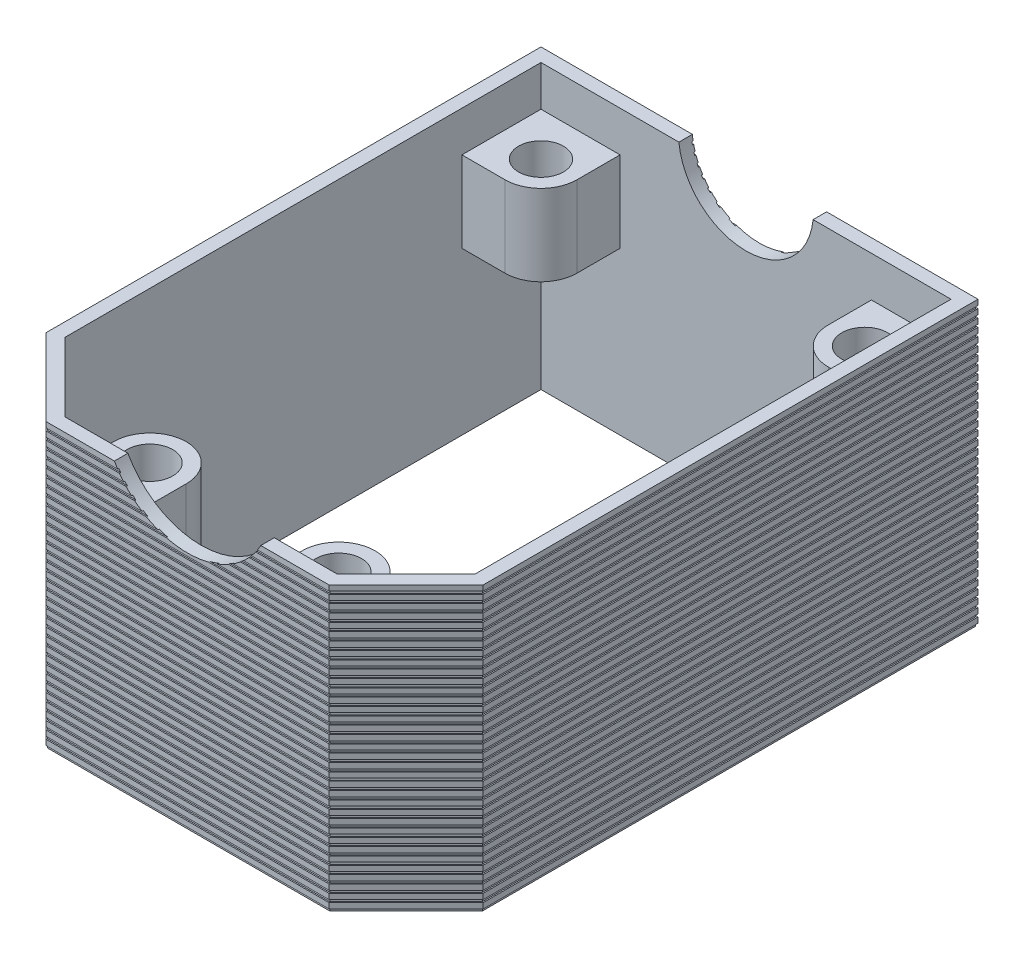
SolidWorks part; units mm, degrees
ref_plane "Front" through (0, 0, 0) normal (0, 0, 1) x (1, 0, 0)
ref_plane "Top" through (0, 0, 0) normal (0, 1, 0) x (1, 0, 0)
ref_plane "Right" through (0, 0, 0) normal (1, 0, 0) x (0, 0, -1)
sketch "Sketch1" plane through (0, 0, 0) normal (0, 1, 0) x (1, 0, 0)
  line L1 (10, -20) -> (-10, -20)
  line L2 (15, -15) -> (15, 20)
  line L3 (15, 20) -> (-15, 20)
  line L4 (-15, -15) -> (-15, 20)
  line L5 (15, -20) -> (-15, 20) construction
  line L6 (15, 20) -> (-15, -20) construction
  line L7 (-15, -15) -> (-10, -20)
  line L10 (10, -20) -> (15, -15)
  circle A0 centre (-12, 17) radius 1.4615
  circle A1 centre (12, 17) radius 1.5
  circle A2 centre (7, -17) radius 1.5
  circle A3 centre (-7, -17) radius 1.5
  point P0 (0, 0)
  dimension "D7" = 3
  dimension "D1" = 30
  dimension "D2" = 40
  dimension "D3" = 5
  dimension "D4" = 5
  dimension "D5" = 5
  dimension "D6" = 5
  dimension "D8" = 3
  dimension "D9" = 3
  dimension "D10" = 3
  dimension "D11" = 3
  dimension "D12" = 3
  dimension "D13" = 3
  dimension "D14" = 3
sketch "Sketch2" plane through (0, 0, 0) normal (0, 1, 0) x (1, 0, 0)
  line L0 (-15.2, 20.2) -> (15.2, 20.2)
  line L1 (15.2, 20.2) -> (15.2, -15.0828)
  line L2 (15.2, -15.0828) -> (10.0828, -20.2)
  line L3 (10.0828, -20.2) -> (-10.0828, -20.2)
  line L4 (-10.0828, -20.2) -> (-15.2, -15.0828)
  line L5 (-15.2, -15.0828) -> (-15.2, 20.2)
  line L6 (-16.2, 21.2) -> (16.2, 21.2)
  line L7 (16.2, 21.2) -> (16.2, -15.4971)
  line L8 (16.2, -15.4971) -> (10.4971, -21.2)
  line L9 (10.4971, -21.2) -> (-10.4971, -21.2)
  line L10 (-10.4971, -21.2) -> (-16.2, -15.4971)
  line L11 (-16.2, -15.4971) -> (-16.2, 21.2)
  line L12 (15, 20) -> (-15, 20) construction
  line L13 (15, -15) -> (15, 20) construction
  line L14 (-15, -15) -> (-15, 20) construction
  line L16 (10, -20) -> (-10, -20) construction
  line L17 (-15, -15) -> (-10, -20) construction
  line L19 (10, -20) -> (15, -15) construction
  dimension "D1" = 0.2
  dimension "D2" = 0.2
  dimension "D3" = 0.2
  dimension "D4" = 0.2
  dimension "D5" = 0.2
  dimension "D6" = 0.2
  dimension "D7" = 1
  dimension "D8" = 1
  dimension "D9" = 1
  dimension "D10" = 1
  dimension "D11" = 1
  dimension "D12" = 1
extrude "Boss-Extrude1" add sketch "Sketch2" along normal blind 9 and the other way blind 12
sketch "Sketch4" plane through (0, 0, 0) normal (0, 1, 0) x (1, 0, 0)
  line L1 (15.2, 20.2) -> (-15.2, 20.2) construction
  line L6 (9.3, 17) -> (9.3, 20.2)
  line L7 (12, 14.3) -> (15.2, 14.3)
  line L8 (15.2, -15.0828) -> (15.2, 20.2) construction
  line L9 (15.2, 14.3) -> (15.2, 20.2)
  line L10 (15.2, 20.2) -> (9.3, 20.2)
  line L11 (-9.7, -17) -> (-9.7, -20.2)
  line L12 (-10.0828, -20.2) -> (10.0828, -20.2) construction
  line L13 (-9.7, -20.2) -> (-4.3, -20.2)
  line L14 (-4.3, -20.2) -> (-4.3, -17)
  line L15 (4.3, -17) -> (4.3, -20.2)
  line L16 (4.3, -20.2) -> (9.7, -20.2)
  line L17 (9.7, -20.2) -> (9.7, -17)
  line L21 (-9.3385, 17) -> (-9.3385, 20.2)
  line L22 (-9.3385, 20.2) -> (-15.2, 20.2)
  line L23 (-15.2, 20.2) -> (-15.2, 14.3385)
  line L24 (-15.2, 20.2) -> (-15.2, -15.0828) construction
  line L25 (-15.2, 14.3385) -> (-12, 14.3385)
  circle A0 centre (-12, 17) radius 1.6615
  circle A1 centre (12, 17) radius 1.7
  arc A2 (9.3, 17) -> (12, 14.3) centre (12, 17) ccw
  circle A4 centre (-7, -17) radius 1.7
  arc A5 (-4.3, -17) -> (-9.7, -17) centre (-7, -17) ccw
  circle A6 centre (7, -17) radius 1.7
  arc A7 (9.7, -17) -> (4.3, -17) centre (7, -17) ccw
  circle A8 centre (-7, -17) radius 1.5 construction
  circle A9 centre (7, -17) radius 1.5 construction
  circle A10 centre (12, 17) radius 1.5 construction
  circle A11 centre (-12, 17) radius 1.4615 construction
  arc A13 (-12, 14.3385) -> (-9.3385, 17) centre (-12, 17) ccw
  dimension "D1" = 0.2
  dimension "D2" = 1
  dimension "D3" = 0.2
  dimension "D4" = 1
  dimension "D5" = 0.2
  dimension "D6" = 1
  dimension "D7" = 0.2
  dimension "D8" = 1
extrude "Boss-Extrude2" add sketch "Sketch4" along normal blind 6
sketch "Sketch5" plane through (0, 0, -21.2) normal (0, 0, -1) x (-1, 0, 0)
  line L6 (-17.0656, 9.5) -> (18.9737, 9.5) construction
  line L7 (-10, 0) -> (10, 0) construction
  circle A1 centre (0, 9.5) radius 5
  dimension "D2" = 10
  dimension "D1" = 9.5
sketch "Sketch6" plane through (0, 0, 21.2) normal (0, 0, 1) x (1, 0, 0)
  line L0 (-10.4971, 9) -> (10.4971, 9) construction
  circle A0 centre (0, 12) radius 6.2
  dimension "D1" = 12.4
  dimension "D2" = 3
extrude "Cut-Extrude4" cut sketch "Sketch6" against normal up to surface (1 mm away) up to face at (-7, 3, 20.2)
extrude "Cut-Extrude5" cut sketch "Sketch5" against normal up to surface (1 mm away) up to face at (-0.0064, 1.5, -20.2)
sketch "Sketch7" plane through (0, 0, -21.2) normal (0, 0, -1) x (-1, 0, 0)
  line L0 (16.2, -12) -> (16.2, 9) construction
  line L1 (-16.2, -12) -> (16.2, -12)
  line L2 (-16.2, -12) -> (-16.2, -11.8)
  line L3 (-16.2, -11.8) -> (16.2, -11.8)
  line L4 (16.2, -12) -> (16.2, -11.8)
  line L289 (-16.2, -11.4) -> (16.2, -11.4)
  line L290 (-16.2, -11.4) -> (-16.2, -11.2)
  line L291 (-16.2, -11.2) -> (16.2, -11.2)
  line L292 (16.2, -11.4) -> (16.2, -11.2)
  line L293 (-16.2, -10.8) -> (16.2, -10.8)
  line L294 (-16.2, -10.8) -> (-16.2, -10.6)
  line L295 (-16.2, -10.6) -> (16.2, -10.6)
  line L296 (16.2, -10.8) -> (16.2, -10.6)
  line L297 (-16.2, -10.2) -> (16.2, -10.2)
  line L298 (-16.2, -10.2) -> (-16.2, -10)
  line L299 (-16.2, -10) -> (16.2, -10)
  line L300 (16.2, -10.2) -> (16.2, -10)
  line L301 (-16.2, -9.6) -> (16.2, -9.6)
  line L302 (-16.2, -9.6) -> (-16.2, -9.4)
  line L303 (-16.2, -9.4) -> (16.2, -9.4)
  line L304 (16.2, -9.6) -> (16.2, -9.4)
  line L305 (-16.2, -9) -> (16.2, -9)
  line L306 (-16.2, -9) -> (-16.2, -8.8)
  line L307 (-16.2, -8.8) -> (16.2, -8.8)
  line L308 (16.2, -9) -> (16.2, -8.8)
  line L309 (-16.2, -8.4) -> (16.2, -8.4)
  line L310 (-16.2, -8.4) -> (-16.2, -8.2)
  line L311 (-16.2, -8.2) -> (16.2, -8.2)
  line L312 (16.2, -8.4) -> (16.2, -8.2)
  line L313 (-16.2, -7.8) -> (16.2, -7.8)
  line L314 (-16.2, -7.8) -> (-16.2, -7.6)
  line L315 (-16.2, -7.6) -> (16.2, -7.6)
  line L316 (16.2, -7.8) -> (16.2, -7.6)
  line L317 (-16.2, -7.2) -> (16.2, -7.2)
  line L318 (-16.2, -7.2) -> (-16.2, -7)
  line L319 (-16.2, -7) -> (16.2, -7)
  line L320 (16.2, -7.2) -> (16.2, -7)
  line L321 (-16.2, -6.6) -> (16.2, -6.6)
  line L322 (-16.2, -6.6) -> (-16.2, -6.4)
  line L323 (-16.2, -6.4) -> (16.2, -6.4)
  line L324 (16.2, -6.6) -> (16.2, -6.4)
  line L325 (-16.2, -6) -> (16.2, -6)
  line L326 (-16.2, -6) -> (-16.2, -5.8)
  line L327 (-16.2, -5.8) -> (16.2, -5.8)
  line L328 (16.2, -6) -> (16.2, -5.8)
  line L329 (-16.2, -5.4) -> (16.2, -5.4)
  line L330 (-16.2, -5.4) -> (-16.2, -5.2)
  line L331 (-16.2, -5.2) -> (16.2, -5.2)
  line L332 (16.2, -5.4) -> (16.2, -5.2)
  line L333 (-16.2, -4.8) -> (16.2, -4.8)
  line L334 (-16.2, -4.8) -> (-16.2, -4.6)
  line L335 (-16.2, -4.6) -> (16.2, -4.6)
  line L336 (16.2, -4.8) -> (16.2, -4.6)
  line L337 (-16.2, -4.2) -> (16.2, -4.2)
  line L338 (-16.2, -4.2) -> (-16.2, -4)
  line L339 (-16.2, -4) -> (16.2, -4)
  line L340 (16.2, -4.2) -> (16.2, -4)
  line L341 (-16.2, -3.6) -> (16.2, -3.6)
  line L342 (-16.2, -3.6) -> (-16.2, -3.4)
  line L343 (-16.2, -3.4) -> (16.2, -3.4)
  line L344 (16.2, -3.6) -> (16.2, -3.4)
  line L345 (-16.2, -3) -> (16.2, -3)
  line L346 (-16.2, -3) -> (-16.2, -2.8)
  line L347 (-16.2, -2.8) -> (16.2, -2.8)
  line L348 (16.2, -3) -> (16.2, -2.8)
  line L349 (-16.2, -2.4) -> (16.2, -2.4)
  line L350 (-16.2, -2.4) -> (-16.2, -2.2)
  line L351 (-16.2, -2.2) -> (16.2, -2.2)
  line L352 (16.2, -2.4) -> (16.2, -2.2)
  line L353 (-16.2, -1.8) -> (16.2, -1.8)
  line L354 (-16.2, -1.8) -> (-16.2, -1.6)
  line L355 (-16.2, -1.6) -> (16.2, -1.6)
  line L356 (16.2, -1.8) -> (16.2, -1.6)
  line L357 (-16.2, -1.2) -> (16.2, -1.2)
  line L358 (-16.2, -1.2) -> (-16.2, -1)
  line L359 (-16.2, -1) -> (16.2, -1)
  line L360 (16.2, -1.2) -> (16.2, -1)
  line L361 (-16.2, -0.6) -> (16.2, -0.6)
  line L362 (-16.2, -0.6) -> (-16.2, -0.4)
  line L363 (-16.2, -0.4) -> (16.2, -0.4)
  line L364 (16.2, -0.6) -> (16.2, -0.4)
  line L365 (-16.2, 0) -> (16.2, 0)
  line L366 (-16.2, 0) -> (-16.2, 0.2)
  line L367 (-16.2, 0.2) -> (16.2, 0.2)
  line L368 (16.2, 0) -> (16.2, 0.2)
  line L369 (-16.2, 0.6) -> (16.2, 0.6)
  line L370 (-16.2, 0.6) -> (-16.2, 0.8)
  line L371 (-16.2, 0.8) -> (16.2, 0.8)
  line L372 (16.2, 0.6) -> (16.2, 0.8)
  line L373 (-16.2, 1.2) -> (16.2, 1.2)
  line L374 (-16.2, 1.2) -> (-16.2, 1.4)
  line L375 (-16.2, 1.4) -> (16.2, 1.4)
  line L376 (16.2, 1.2) -> (16.2, 1.4)
  line L377 (-16.2, 1.8) -> (16.2, 1.8)
  line L378 (-16.2, 1.8) -> (-16.2, 2)
  line L379 (-16.2, 2) -> (16.2, 2)
  line L380 (16.2, 1.8) -> (16.2, 2)
  line L381 (-16.2, 2.4) -> (16.2, 2.4)
  line L382 (-16.2, 2.4) -> (-16.2, 2.6)
  line L383 (-16.2, 2.6) -> (16.2, 2.6)
  line L384 (16.2, 2.4) -> (16.2, 2.6)
  line L385 (-16.2, 3) -> (16.2, 3)
  line L386 (-16.2, 3) -> (-16.2, 3.2)
  line L387 (-16.2, 3.2) -> (16.2, 3.2)
  line L388 (16.2, 3) -> (16.2, 3.2)
  line L389 (-16.2, 3.6) -> (16.2, 3.6)
  line L390 (-16.2, 3.6) -> (-16.2, 3.8)
  line L391 (-16.2, 3.8) -> (16.2, 3.8)
  line L392 (16.2, 3.6) -> (16.2, 3.8)
  line L393 (-16.2, 4.2) -> (16.2, 4.2)
  line L394 (-16.2, 4.2) -> (-16.2, 4.4)
  line L395 (-16.2, 4.4) -> (16.2, 4.4)
  line L396 (16.2, 4.2) -> (16.2, 4.4)
  line L397 (-16.2, 4.8) -> (16.2, 4.8)
  line L398 (-16.2, 4.8) -> (-16.2, 5)
  line L399 (-16.2, 5) -> (16.2, 5)
  line L400 (16.2, 4.8) -> (16.2, 5)
  line L401 (-16.2, 5.4) -> (16.2, 5.4)
  line L402 (-16.2, 5.4) -> (-16.2, 5.6)
  line L403 (-16.2, 5.6) -> (16.2, 5.6)
  line L404 (16.2, 5.4) -> (16.2, 5.6)
  line L405 (-16.2, 6) -> (16.2, 6)
  line L406 (-16.2, 6) -> (-16.2, 6.2)
  line L407 (-16.2, 6.2) -> (16.2, 6.2)
  line L408 (16.2, 6) -> (16.2, 6.2)
  line L409 (-16.2, 6.6) -> (16.2, 6.6)
  line L410 (-16.2, 6.6) -> (-16.2, 6.8)
  line L411 (-16.2, 6.8) -> (16.2, 6.8)
  line L412 (16.2, 6.6) -> (16.2, 6.8)
  line L413 (-16.2, 7.2) -> (16.2, 7.2)
  line L414 (-16.2, 7.2) -> (-16.2, 7.4)
  line L415 (-16.2, 7.4) -> (16.2, 7.4)
  line L416 (16.2, 7.2) -> (16.2, 7.4)
  line L417 (-16.2, 7.8) -> (16.2, 7.8)
  line L418 (-16.2, 7.8) -> (-16.2, 8)
  line L419 (-16.2, 8) -> (16.2, 8)
  line L420 (16.2, 7.8) -> (16.2, 8)
  line L421 (-16.2, 8.4) -> (16.2, 8.4)
  line L422 (-16.2, 8.4) -> (-16.2, 8.6)
  line L423 (-16.2, 8.6) -> (16.2, 8.6)
  line L424 (16.2, 8.4) -> (16.2, 8.6)
  line L425 (-16.2, 9) -> (16.2, 9)
  line L426 (-16.2, 9) -> (-16.2, 9.2)
  line L427 (-16.2, 9.2) -> (16.2, 9.2)
  line L428 (16.2, 9) -> (16.2, 9.2)
  line L429 (-16.2, 9.6) -> (16.2, 9.6)
  line L430 (-16.2, 9.6) -> (-16.2, 9.8)
  line L431 (-16.2, 9.8) -> (16.2, 9.8)
  line L432 (16.2, 9.6) -> (16.2, 9.8)
  line L433 (-16.2, 10.2) -> (16.2, 10.2)
  line L434 (-16.2, 10.2) -> (-16.2, 10.4)
  line L435 (-16.2, 10.4) -> (16.2, 10.4)
  line L436 (16.2, 10.2) -> (16.2, 10.4)
  line L437 (-16.2, 10.8) -> (16.2, 10.8)
  line L438 (-16.2, 10.8) -> (-16.2, 11)
  line L439 (-16.2, 11) -> (16.2, 11)
  line L440 (16.2, 10.8) -> (16.2, 11)
  line L441 (-16.2, 11.4) -> (16.2, 11.4)
  line L442 (-16.2, 11.4) -> (-16.2, 11.6)
  line L443 (-16.2, 11.6) -> (16.2, 11.6)
  line L444 (16.2, 11.4) -> (16.2, 11.6)
  dimension "D1" = 0.2
  dimension "D2" = 40
extrude "Cut-Extrude6" cut sketch "Sketch7" against normal blind 0.09
sketch "Sketch8" plane through (16.2, 0, 0) normal (1, 0, 0) x (0, 0, -1)
  line L129 (-15.4971, -11.4) -> (-15.4971, -11.2)
  line L130 (-15.4971, -12) -> (21.11, -12)
  line L131 (-15.4971, -12) -> (-15.4971, -11.8)
  line L132 (-15.4971, -11.8) -> (21.11, -11.8)
  line L133 (21.11, -12) -> (21.11, -11.8)
  line L134 (-15.4971, -11.4) -> (21.11, -11.4)
  line L135 (21.11, -11.4) -> (21.11, -11.2)
  line L136 (-15.4971, -11.2) -> (21.11, -11.2)
  line L137 (-15.4971, -10.8) -> (-15.4971, -10.6)
  line L138 (-15.4971, -10.8) -> (21.11, -10.8)
  line L139 (21.11, -10.8) -> (21.11, -10.6)
  line L140 (-15.4971, -10.6) -> (21.11, -10.6)
  line L141 (-15.4971, -10.2) -> (-15.4971, -10)
  line L142 (-15.4971, -10.2) -> (21.11, -10.2)
  line L143 (21.11, -10.2) -> (21.11, -10)
  line L144 (-15.4971, -10) -> (21.11, -10)
  line L145 (-15.4971, -9.6) -> (-15.4971, -9.4)
  line L146 (-15.4971, -9.6) -> (21.11, -9.6)
  line L147 (21.11, -9.6) -> (21.11, -9.4)
  line L148 (-15.4971, -9.4) -> (21.11, -9.4)
  line L149 (-15.4971, -9) -> (-15.4971, -8.8)
  line L150 (-15.4971, -9) -> (21.11, -9)
  line L151 (21.11, -9) -> (21.11, -8.8)
  line L152 (-15.4971, -8.8) -> (21.11, -8.8)
  line L153 (-15.4971, -8.4) -> (-15.4971, -8.2)
  line L154 (-15.4971, -8.4) -> (21.11, -8.4)
  line L155 (21.11, -8.4) -> (21.11, -8.2)
  line L156 (-15.4971, -8.2) -> (21.11, -8.2)
  line L157 (-15.4971, -7.8) -> (-15.4971, -7.6)
  line L158 (-15.4971, -7.8) -> (21.11, -7.8)
  line L159 (21.11, -7.8) -> (21.11, -7.6)
  line L160 (-15.4971, -7.6) -> (21.11, -7.6)
  line L161 (-15.4971, -7.2) -> (-15.4971, -7)
  line L162 (-15.4971, -7.2) -> (21.11, -7.2)
  line L163 (21.11, -7.2) -> (21.11, -7)
  line L164 (-15.4971, -7) -> (21.11, -7)
  line L165 (-15.4971, -6.6) -> (-15.4971, -6.4)
  line L166 (-15.4971, -6.6) -> (21.11, -6.6)
  line L167 (21.11, -6.6) -> (21.11, -6.4)
  line L168 (-15.4971, -6.4) -> (21.11, -6.4)
  line L169 (-15.4971, -6) -> (-15.4971, -5.8)
  line L170 (-15.4971, -6) -> (21.11, -6)
  line L171 (21.11, -6) -> (21.11, -5.8)
  line L172 (-15.4971, -5.8) -> (21.11, -5.8)
  line L173 (-15.4971, -5.4) -> (-15.4971, -5.2)
  line L174 (-15.4971, -5.4) -> (21.11, -5.4)
  line L175 (21.11, -5.4) -> (21.11, -5.2)
  line L176 (-15.4971, -5.2) -> (21.11, -5.2)
  line L177 (-15.4971, -4.8) -> (-15.4971, -4.6)
  line L178 (-15.4971, -4.8) -> (21.11, -4.8)
  line L179 (21.11, -4.8) -> (21.11, -4.6)
  line L180 (-15.4971, -4.6) -> (21.11, -4.6)
  line L181 (-15.4971, -4.2) -> (-15.4971, -4)
  line L182 (-15.4971, -4.2) -> (21.11, -4.2)
  line L183 (21.11, -4.2) -> (21.11, -4)
  line L184 (-15.4971, -4) -> (21.11, -4)
  line L185 (-15.4971, -3.6) -> (-15.4971, -3.4)
  line L186 (-15.4971, -3.6) -> (21.11, -3.6)
  line L187 (21.11, -3.6) -> (21.11, -3.4)
  line L188 (-15.4971, -3.4) -> (21.11, -3.4)
  line L189 (-15.4971, -3) -> (-15.4971, -2.8)
  line L190 (-15.4971, -3) -> (21.11, -3)
  line L191 (21.11, -3) -> (21.11, -2.8)
  line L192 (-15.4971, -2.8) -> (21.11, -2.8)
  line L193 (-15.4971, -2.4) -> (-15.4971, -2.2)
  line L194 (-15.4971, -2.4) -> (21.11, -2.4)
  line L195 (21.11, -2.4) -> (21.11, -2.2)
  line L196 (-15.4971, -2.2) -> (21.11, -2.2)
  line L197 (-15.4971, -1.8) -> (-15.4971, -1.6)
  line L198 (-15.4971, -1.8) -> (21.11, -1.8)
  line L199 (21.11, -1.8) -> (21.11, -1.6)
  line L200 (-15.4971, -1.6) -> (21.11, -1.6)
  line L201 (-15.4971, -1.2) -> (-15.4971, -1)
  line L202 (-15.4971, -1.2) -> (21.11, -1.2)
  line L203 (21.11, -1.2) -> (21.11, -1)
  line L204 (-15.4971, -1) -> (21.11, -1)
  line L205 (-15.4971, -0.6) -> (-15.4971, -0.4)
  line L206 (-15.4971, -0.6) -> (21.11, -0.6)
  line L207 (21.11, -0.6) -> (21.11, -0.4)
  line L208 (-15.4971, -0.4) -> (21.11, -0.4)
  line L209 (-15.4971, 0) -> (-15.4971, 0.2)
  line L210 (-15.4971, 0) -> (21.11, 0)
  line L211 (21.11, 0) -> (21.11, 0.2)
  line L212 (-15.4971, 0.2) -> (21.11, 0.2)
  line L213 (-15.4971, 0.6) -> (-15.4971, 0.8)
  line L214 (-15.4971, 0.6) -> (21.11, 0.6)
  line L215 (21.11, 0.6) -> (21.11, 0.8)
  line L216 (-15.4971, 0.8) -> (21.11, 0.8)
  line L217 (-15.4971, 1.2) -> (-15.4971, 1.4)
  line L218 (-15.4971, 1.2) -> (21.11, 1.2)
  line L219 (21.11, 1.2) -> (21.11, 1.4)
  line L220 (-15.4971, 1.4) -> (21.11, 1.4)
  line L221 (-15.4971, 1.8) -> (-15.4971, 2)
  line L222 (-15.4971, 1.8) -> (21.11, 1.8)
  line L223 (21.11, 1.8) -> (21.11, 2)
  line L224 (-15.4971, 2) -> (21.11, 2)
  line L225 (-15.4971, 2.4) -> (-15.4971, 2.6)
  line L226 (-15.4971, 2.4) -> (21.11, 2.4)
  line L227 (21.11, 2.4) -> (21.11, 2.6)
  line L228 (-15.4971, 2.6) -> (21.11, 2.6)
  line L229 (-15.4971, 3) -> (-15.4971, 3.2)
  line L230 (-15.4971, 3) -> (21.11, 3)
  line L231 (21.11, 3) -> (21.11, 3.2)
  line L232 (-15.4971, 3.2) -> (21.11, 3.2)
  line L233 (-15.4971, 3.6) -> (-15.4971, 3.8)
  line L234 (-15.4971, 3.6) -> (21.11, 3.6)
  line L235 (21.11, 3.6) -> (21.11, 3.8)
  line L236 (-15.4971, 3.8) -> (21.11, 3.8)
  line L237 (-15.4971, 4.2) -> (-15.4971, 4.4)
  line L238 (-15.4971, 4.2) -> (21.11, 4.2)
  line L239 (21.11, 4.2) -> (21.11, 4.4)
  line L240 (-15.4971, 4.4) -> (21.11, 4.4)
  line L241 (-15.4971, 4.8) -> (-15.4971, 5)
  line L242 (-15.4971, 4.8) -> (21.11, 4.8)
  line L243 (21.11, 4.8) -> (21.11, 5)
  line L244 (-15.4971, 5) -> (21.11, 5)
  line L245 (-15.4971, 5.4) -> (-15.4971, 5.6)
  line L246 (-15.4971, 5.4) -> (21.11, 5.4)
  line L247 (21.11, 5.4) -> (21.11, 5.6)
  line L248 (-15.4971, 5.6) -> (21.11, 5.6)
  line L249 (-15.4971, 6) -> (-15.4971, 6.2)
  line L250 (-15.4971, 6) -> (21.11, 6)
  line L251 (21.11, 6) -> (21.11, 6.2)
  line L252 (-15.4971, 6.2) -> (21.11, 6.2)
  line L253 (-15.4971, 6.6) -> (-15.4971, 6.8)
  line L254 (-15.4971, 6.6) -> (21.11, 6.6)
  line L255 (21.11, 6.6) -> (21.11, 6.8)
  line L256 (-15.4971, 6.8) -> (21.11, 6.8)
  line L257 (-15.4971, 7.2) -> (-15.4971, 7.4)
  line L258 (-15.4971, 7.2) -> (21.11, 7.2)
  line L259 (21.11, 7.2) -> (21.11, 7.4)
  line L260 (-15.4971, 7.4) -> (21.11, 7.4)
  line L261 (-15.4971, 7.8) -> (-15.4971, 8)
  line L262 (-15.4971, 7.8) -> (21.11, 7.8)
  line L263 (21.11, 7.8) -> (21.11, 8)
  line L264 (-15.4971, 8) -> (21.11, 8)
  line L265 (-15.4971, 8.4) -> (-15.4971, 8.6)
  line L266 (-15.4971, 8.4) -> (21.11, 8.4)
  line L267 (21.11, 8.4) -> (21.11, 8.6)
  line L268 (-15.4971, 8.6) -> (21.11, 8.6)
  line L269 (-15.4971, 9) -> (-15.4971, 9.2)
  line L270 (-15.4971, 9) -> (21.11, 9)
  line L271 (21.11, 9) -> (21.11, 9.2)
  line L272 (-15.4971, 9.2) -> (21.11, 9.2)
  line L273 (-15.4971, 9.6) -> (-15.4971, 9.8)
  line L274 (-15.4971, 9.6) -> (21.11, 9.6)
  line L275 (21.11, 9.6) -> (21.11, 9.8)
  line L276 (-15.4971, 9.8) -> (21.11, 9.8)
  dimension "D1" = 37
extrude "Cut-Extrude7" cut sketch "Sketch8" against normal offset from surface (0.09 mm away) 0.09 up to face at (16.2, -1.5493, -20.6388)
sketch "Sketch9" plane through (15.8485, 0, 15.8485) normal (0.7071, 0, 0.7071) x (0.7071, 0, -0.7071)
  line L0 (-7.5681, -11.4) -> (-7.5681, -11.2)
  line L1 (-7.5681, -12) -> (0.4971, -12)
  line L2 (-7.5681, -12) -> (-7.5681, -11.8)
  line L3 (-7.5681, -11.8) -> (0.4971, -11.8)
  line L4 (0.4971, -12) -> (0.4971, -11.8)
  line L5 (-7.5681, -11.4) -> (0.4971, -11.4)
  line L6 (0.4971, -11.4) -> (0.4971, -11.2)
  line L7 (-7.5681, -11.2) -> (0.4971, -11.2)
  line L8 (-7.5681, -10.8) -> (-7.5681, -10.6)
  line L9 (-7.5681, -10.8) -> (0.4971, -10.8)
  line L10 (0.4971, -10.8) -> (0.4971, -10.6)
  line L11 (-7.5681, -10.6) -> (0.4971, -10.6)
  line L12 (-7.5681, -10.2) -> (-7.5681, -10)
  line L13 (-7.5681, -10.2) -> (0.4971, -10.2)
  line L14 (0.4971, -10.2) -> (0.4971, -10)
  line L15 (-7.5681, -10) -> (0.4971, -10)
  line L16 (-7.5681, -9.6) -> (-7.5681, -9.4)
  line L17 (-7.5681, -9.6) -> (0.4971, -9.6)
  line L18 (0.4971, -9.6) -> (0.4971, -9.4)
  line L19 (-7.5681, -9.4) -> (0.4971, -9.4)
  line L20 (-7.5681, -9) -> (-7.5681, -8.8)
  line L21 (-7.5681, -9) -> (0.4971, -9)
  line L22 (0.4971, -9) -> (0.4971, -8.8)
  line L23 (-7.5681, -8.8) -> (0.4971, -8.8)
  line L24 (-7.5681, -8.4) -> (-7.5681, -8.2)
  line L25 (-7.5681, -8.4) -> (0.4971, -8.4)
  line L26 (0.4971, -8.4) -> (0.4971, -8.2)
  line L27 (-7.5681, -8.2) -> (0.4971, -8.2)
  line L28 (-7.5681, -7.8) -> (-7.5681, -7.6)
  line L29 (-7.5681, -7.8) -> (0.4971, -7.8)
  line L30 (0.4971, -7.8) -> (0.4971, -7.6)
  line L31 (-7.5681, -7.6) -> (0.4971, -7.6)
  line L32 (-7.5681, -7.2) -> (-7.5681, -7)
  line L33 (-7.5681, -7.2) -> (0.4971, -7.2)
  line L34 (0.4971, -7.2) -> (0.4971, -7)
  line L35 (-7.5681, -7) -> (0.4971, -7)
  line L36 (-7.5681, -6.6) -> (-7.5681, -6.4)
  line L37 (-7.5681, -6.6) -> (0.4971, -6.6)
  line L38 (0.4971, -6.6) -> (0.4971, -6.4)
  line L39 (-7.5681, -6.4) -> (0.4971, -6.4)
  line L40 (-7.5681, -6) -> (-7.5681, -5.8)
  line L41 (-7.5681, -6) -> (0.4971, -6)
  line L42 (0.4971, -6) -> (0.4971, -5.8)
  line L43 (-7.5681, -5.8) -> (0.4971, -5.8)
  line L44 (-7.5681, -5.4) -> (-7.5681, -5.2)
  line L45 (-7.5681, -5.4) -> (0.4971, -5.4)
  line L46 (0.4971, -5.4) -> (0.4971, -5.2)
  line L47 (-7.5681, -5.2) -> (0.4971, -5.2)
  line L48 (-7.5681, -4.8) -> (-7.5681, -4.6)
  line L49 (-7.5681, -4.8) -> (0.4971, -4.8)
  line L50 (0.4971, -4.8) -> (0.4971, -4.6)
  line L51 (-7.5681, -4.6) -> (0.4971, -4.6)
  line L52 (-7.5681, -4.2) -> (-7.5681, -4)
  line L53 (-7.5681, -4.2) -> (0.4971, -4.2)
  line L54 (0.4971, -4.2) -> (0.4971, -4)
  line L55 (-7.5681, -4) -> (0.4971, -4)
  line L56 (-7.5681, -3.6) -> (-7.5681, -3.4)
  line L57 (-7.5681, -3.6) -> (0.4971, -3.6)
  line L58 (0.4971, -3.6) -> (0.4971, -3.4)
  line L59 (-7.5681, -3.4) -> (0.4971, -3.4)
  line L60 (-7.5681, -3) -> (-7.5681, -2.8)
  line L61 (-7.5681, -3) -> (0.4971, -3)
  line L62 (0.4971, -3) -> (0.4971, -2.8)
  line L63 (-7.5681, -2.8) -> (0.4971, -2.8)
  line L64 (-7.5681, -2.4) -> (-7.5681, -2.2)
  line L65 (-7.5681, -2.4) -> (0.4971, -2.4)
  line L66 (0.4971, -2.4) -> (0.4971, -2.2)
  line L67 (-7.5681, -2.2) -> (0.4971, -2.2)
  line L68 (-7.5681, -1.8) -> (-7.5681, -1.6)
  line L69 (-7.5681, -1.8) -> (0.4971, -1.8)
  line L70 (0.4971, -1.8) -> (0.4971, -1.6)
  line L71 (-7.5681, -1.6) -> (0.4971, -1.6)
  line L72 (-7.5681, -1.2) -> (-7.5681, -1)
  line L73 (-7.5681, -1.2) -> (0.4971, -1.2)
  line L74 (0.4971, -1.2) -> (0.4971, -1)
  line L75 (-7.5681, -1) -> (0.4971, -1)
  line L76 (-7.5681, -0.6) -> (-7.5681, -0.4)
  line L77 (-7.5681, -0.6) -> (0.4971, -0.6)
  line L78 (0.4971, -0.6) -> (0.4971, -0.4)
  line L79 (-7.5681, -0.4) -> (0.4971, -0.4)
  line L80 (-7.5681, 0) -> (-7.5681, 0.2)
  line L81 (-7.5681, 0) -> (0.4971, 0)
  line L82 (0.4971, 0) -> (0.4971, 0.2)
  line L83 (-7.5681, 0.2) -> (0.4971, 0.2)
  line L84 (-7.5681, 0.6) -> (-7.5681, 0.8)
  line L85 (-7.5681, 0.6) -> (0.4971, 0.6)
  line L86 (0.4971, 0.6) -> (0.4971, 0.8)
  line L87 (-7.5681, 0.8) -> (0.4971, 0.8)
  line L88 (-7.5681, 1.2) -> (-7.5681, 1.4)
  line L89 (-7.5681, 1.2) -> (0.4971, 1.2)
  line L90 (0.4971, 1.2) -> (0.4971, 1.4)
  line L91 (-7.5681, 1.4) -> (0.4971, 1.4)
  line L92 (-7.5681, 1.8) -> (-7.5681, 2)
  line L93 (-7.5681, 1.8) -> (0.4971, 1.8)
  line L94 (0.4971, 1.8) -> (0.4971, 2)
  line L95 (-7.5681, 2) -> (0.4971, 2)
  line L96 (-7.5681, 2.4) -> (-7.5681, 2.6)
  line L97 (-7.5681, 2.4) -> (0.4971, 2.4)
  line L98 (0.4971, 2.4) -> (0.4971, 2.6)
  line L99 (-7.5681, 2.6) -> (0.4971, 2.6)
  line L100 (-7.5681, 3) -> (-7.5681, 3.2)
  line L101 (-7.5681, 3) -> (0.4971, 3)
  line L102 (0.4971, 3) -> (0.4971, 3.2)
  line L103 (-7.5681, 3.2) -> (0.4971, 3.2)
  line L104 (-7.5681, 3.6) -> (-7.5681, 3.8)
  line L105 (-7.5681, 3.6) -> (0.4971, 3.6)
  line L106 (0.4971, 3.6) -> (0.4971, 3.8)
  line L107 (-7.5681, 3.8) -> (0.4971, 3.8)
  line L108 (-7.5681, 4.2) -> (-7.5681, 4.4)
  line L109 (-7.5681, 4.2) -> (0.4971, 4.2)
  line L110 (0.4971, 4.2) -> (0.4971, 4.4)
  line L111 (-7.5681, 4.4) -> (0.4971, 4.4)
  line L112 (-7.5681, 4.8) -> (-7.5681, 5)
  line L113 (-7.5681, 4.8) -> (0.4971, 4.8)
  line L114 (0.4971, 4.8) -> (0.4971, 5)
  line L115 (-7.5681, 5) -> (0.4971, 5)
  line L116 (-7.5681, 5.4) -> (-7.5681, 5.6)
  line L117 (-7.5681, 5.4) -> (0.4971, 5.4)
  line L118 (0.4971, 5.4) -> (0.4971, 5.6)
  line L119 (-7.5681, 5.6) -> (0.4971, 5.6)
  line L120 (-7.5681, 6) -> (-7.5681, 6.2)
  line L121 (-7.5681, 6) -> (0.4971, 6)
  line L122 (0.4971, 6) -> (0.4971, 6.2)
  line L123 (-7.5681, 6.2) -> (0.4971, 6.2)
  line L124 (-7.5681, 6.6) -> (-7.5681, 6.8)
  line L125 (-7.5681, 6.6) -> (0.4971, 6.6)
  line L126 (0.4971, 6.6) -> (0.4971, 6.8)
  line L127 (-7.5681, 6.8) -> (0.4971, 6.8)
  line L128 (-7.5681, 7.2) -> (-7.5681, 7.4)
  line L129 (-7.5681, 7.2) -> (0.4971, 7.2)
  line L130 (0.4971, 7.2) -> (0.4971, 7.4)
  line L131 (-7.5681, 7.4) -> (0.4971, 7.4)
  line L132 (-7.5681, 7.8) -> (-7.5681, 8)
  line L133 (-7.5681, 7.8) -> (0.4971, 7.8)
  line L134 (0.4971, 7.8) -> (0.4971, 8)
  line L135 (-7.5681, 8) -> (0.4971, 8)
  line L136 (-7.5681, 8.4) -> (-7.5681, 8.6)
  line L137 (-7.5681, 8.4) -> (0.4971, 8.4)
  line L138 (0.4971, 8.4) -> (0.4971, 8.6)
  line L139 (-7.5681, 8.6) -> (0.4971, 8.6)
  line L140 (-7.5681, 9) -> (-7.5681, 9.2)
  line L141 (-7.5681, 9) -> (0.4971, 9)
  line L142 (0.4971, 9) -> (0.4971, 9.2)
  line L143 (-7.5681, 9.2) -> (0.4971, 9.2)
  line L144 (-7.5681, 9.6) -> (-7.5681, 9.8)
  line L145 (-7.5681, 9.6) -> (0.4971, 9.6)
  line L146 (0.4971, 9.6) -> (0.4971, 9.8)
  line L147 (-7.5681, 9.8) -> (0.4971, 9.8)
  dimension "D1" = 37
extrude "Cut-Extrude8" cut sketch "Sketch9" against normal offset from surface (0.09 mm away) 0.09 up to face at (16.0438, -1.5479, 15.6533)
sketch "Sketch10" plane through (0, 0, 21.2) normal (0, 0, 1) x (1, 0, 0)
  line L0 (-10.4971, -11.4) -> (-10.4971, -11.2)
  line L1 (-10.4971, -12) -> (10.4971, -12)
  line L2 (-10.4971, -12) -> (-10.4971, -11.8)
  line L3 (-10.4971, -11.8) -> (10.4971, -11.8)
  line L4 (10.4971, -12) -> (10.4971, -11.8)
  line L5 (-10.4971, -11.4) -> (10.4971, -11.4)
  line L6 (10.4971, -11.4) -> (10.4971, -11.2)
  line L7 (-10.4971, -11.2) -> (10.4971, -11.2)
  line L8 (-10.4971, -10.8) -> (-10.4971, -10.6)
  line L9 (-10.4971, -10.8) -> (10.4971, -10.8)
  line L10 (10.4971, -10.8) -> (10.4971, -10.6)
  line L11 (-10.4971, -10.6) -> (10.4971, -10.6)
  line L12 (-10.4971, -10.2) -> (-10.4971, -10)
  line L13 (-10.4971, -10.2) -> (10.4971, -10.2)
  line L14 (10.4971, -10.2) -> (10.4971, -10)
  line L15 (-10.4971, -10) -> (10.4971, -10)
  line L16 (-10.4971, -9.6) -> (-10.4971, -9.4)
  line L17 (-10.4971, -9.6) -> (10.4971, -9.6)
  line L18 (10.4971, -9.6) -> (10.4971, -9.4)
  line L19 (-10.4971, -9.4) -> (10.4971, -9.4)
  line L20 (-10.4971, -9) -> (-10.4971, -8.8)
  line L21 (-10.4971, -9) -> (10.4971, -9)
  line L22 (10.4971, -9) -> (10.4971, -8.8)
  line L23 (-10.4971, -8.8) -> (10.4971, -8.8)
  line L24 (-10.4971, -8.4) -> (-10.4971, -8.2)
  line L25 (-10.4971, -8.4) -> (10.4971, -8.4)
  line L26 (10.4971, -8.4) -> (10.4971, -8.2)
  line L27 (-10.4971, -8.2) -> (10.4971, -8.2)
  line L28 (-10.4971, -7.8) -> (-10.4971, -7.6)
  line L29 (-10.4971, -7.8) -> (10.4971, -7.8)
  line L30 (10.4971, -7.8) -> (10.4971, -7.6)
  line L31 (-10.4971, -7.6) -> (10.4971, -7.6)
  line L32 (-10.4971, -7.2) -> (-10.4971, -7)
  line L33 (-10.4971, -7.2) -> (10.4971, -7.2)
  line L34 (10.4971, -7.2) -> (10.4971, -7)
  line L35 (-10.4971, -7) -> (10.4971, -7)
  line L36 (-10.4971, -6.6) -> (-10.4971, -6.4)
  line L37 (-10.4971, -6.6) -> (10.4971, -6.6)
  line L38 (10.4971, -6.6) -> (10.4971, -6.4)
  line L39 (-10.4971, -6.4) -> (10.4971, -6.4)
  line L40 (-10.4971, -6) -> (-10.4971, -5.8)
  line L41 (-10.4971, -6) -> (10.4971, -6)
  line L42 (10.4971, -6) -> (10.4971, -5.8)
  line L43 (-10.4971, -5.8) -> (10.4971, -5.8)
  line L44 (-10.4971, -5.4) -> (-10.4971, -5.2)
  line L45 (-10.4971, -5.4) -> (10.4971, -5.4)
  line L46 (10.4971, -5.4) -> (10.4971, -5.2)
  line L47 (-10.4971, -5.2) -> (10.4971, -5.2)
  line L48 (-10.4971, -4.8) -> (-10.4971, -4.6)
  line L49 (-10.4971, -4.8) -> (10.4971, -4.8)
  line L50 (10.4971, -4.8) -> (10.4971, -4.6)
  line L51 (-10.4971, -4.6) -> (10.4971, -4.6)
  line L52 (-10.4971, -4.2) -> (-10.4971, -4)
  line L53 (-10.4971, -4.2) -> (10.4971, -4.2)
  line L54 (10.4971, -4.2) -> (10.4971, -4)
  line L55 (-10.4971, -4) -> (10.4971, -4)
  line L56 (-10.4971, -3.6) -> (-10.4971, -3.4)
  line L57 (-10.4971, -3.6) -> (10.4971, -3.6)
  line L58 (10.4971, -3.6) -> (10.4971, -3.4)
  line L59 (-10.4971, -3.4) -> (10.4971, -3.4)
  line L60 (-10.4971, -3) -> (-10.4971, -2.8)
  line L61 (-10.4971, -3) -> (10.4971, -3)
  line L62 (10.4971, -3) -> (10.4971, -2.8)
  line L63 (-10.4971, -2.8) -> (10.4971, -2.8)
  line L64 (-10.4971, -2.4) -> (-10.4971, -2.2)
  line L65 (-10.4971, -2.4) -> (10.4971, -2.4)
  line L66 (10.4971, -2.4) -> (10.4971, -2.2)
  line L67 (-10.4971, -2.2) -> (10.4971, -2.2)
  line L68 (-10.4971, -1.8) -> (-10.4971, -1.6)
  line L69 (-10.4971, -1.8) -> (10.4971, -1.8)
  line L70 (10.4971, -1.8) -> (10.4971, -1.6)
  line L71 (-10.4971, -1.6) -> (10.4971, -1.6)
  line L72 (-10.4971, -1.2) -> (-10.4971, -1)
  line L73 (-10.4971, -1.2) -> (10.4971, -1.2)
  line L74 (10.4971, -1.2) -> (10.4971, -1)
  line L75 (-10.4971, -1) -> (10.4971, -1)
  line L76 (-10.4971, -0.6) -> (-10.4971, -0.4)
  line L77 (-10.4971, -0.6) -> (10.4971, -0.6)
  line L78 (10.4971, -0.6) -> (10.4971, -0.4)
  line L79 (-10.4971, -0.4) -> (10.4971, -0.4)
  line L80 (-10.4971, 0) -> (-10.4971, 0.2)
  line L81 (-10.4971, 0) -> (10.4971, 0)
  line L82 (10.4971, 0) -> (10.4971, 0.2)
  line L83 (-10.4971, 0.2) -> (10.4971, 0.2)
  line L84 (-10.4971, 0.6) -> (-10.4971, 0.8)
  line L85 (-10.4971, 0.6) -> (10.4971, 0.6)
  line L86 (10.4971, 0.6) -> (10.4971, 0.8)
  line L87 (-10.4971, 0.8) -> (10.4971, 0.8)
  line L88 (-10.4971, 1.2) -> (-10.4971, 1.4)
  line L89 (-10.4971, 1.2) -> (10.4971, 1.2)
  line L90 (10.4971, 1.2) -> (10.4971, 1.4)
  line L91 (-10.4971, 1.4) -> (10.4971, 1.4)
  line L92 (-10.4971, 1.8) -> (-10.4971, 2)
  line L93 (-10.4971, 1.8) -> (10.4971, 1.8)
  line L94 (10.4971, 1.8) -> (10.4971, 2)
  line L95 (-10.4971, 2) -> (10.4971, 2)
  line L96 (-10.4971, 2.4) -> (-10.4971, 2.6)
  line L97 (-10.4971, 2.4) -> (10.4971, 2.4)
  line L98 (10.4971, 2.4) -> (10.4971, 2.6)
  line L99 (-10.4971, 2.6) -> (10.4971, 2.6)
  line L100 (-10.4971, 3) -> (-10.4971, 3.2)
  line L101 (-10.4971, 3) -> (10.4971, 3)
  line L102 (10.4971, 3) -> (10.4971, 3.2)
  line L103 (-10.4971, 3.2) -> (10.4971, 3.2)
  line L104 (-10.4971, 3.6) -> (-10.4971, 3.8)
  line L105 (-10.4971, 3.6) -> (10.4971, 3.6)
  line L106 (10.4971, 3.6) -> (10.4971, 3.8)
  line L107 (-10.4971, 3.8) -> (10.4971, 3.8)
  line L108 (-10.4971, 4.2) -> (-10.4971, 4.4)
  line L109 (-10.4971, 4.2) -> (10.4971, 4.2)
  line L110 (10.4971, 4.2) -> (10.4971, 4.4)
  line L111 (-10.4971, 4.4) -> (10.4971, 4.4)
  line L112 (-10.4971, 4.8) -> (-10.4971, 5)
  line L113 (-10.4971, 4.8) -> (10.4971, 4.8)
  line L114 (10.4971, 4.8) -> (10.4971, 5)
  line L115 (-10.4971, 5) -> (10.4971, 5)
  line L116 (-10.4971, 5.4) -> (-10.4971, 5.6)
  line L117 (-10.4971, 5.4) -> (10.4971, 5.4)
  line L118 (10.4971, 5.4) -> (10.4971, 5.6)
  line L119 (-10.4971, 5.6) -> (10.4971, 5.6)
  line L120 (-10.4971, 6) -> (-10.4971, 6.2)
  line L121 (-10.4971, 6) -> (10.4971, 6)
  line L122 (10.4971, 6) -> (10.4971, 6.2)
  line L123 (-10.4971, 6.2) -> (10.4971, 6.2)
  line L124 (-10.4971, 6.6) -> (-10.4971, 6.8)
  line L125 (-10.4971, 6.6) -> (10.4971, 6.6)
  line L126 (10.4971, 6.6) -> (10.4971, 6.8)
  line L127 (-10.4971, 6.8) -> (10.4971, 6.8)
  line L128 (-10.4971, 7.2) -> (-10.4971, 7.4)
  line L129 (-10.4971, 7.2) -> (10.4971, 7.2)
  line L130 (10.4971, 7.2) -> (10.4971, 7.4)
  line L131 (-10.4971, 7.4) -> (10.4971, 7.4)
  line L132 (-10.4971, 7.8) -> (-10.4971, 8)
  line L133 (-10.4971, 7.8) -> (10.4971, 7.8)
  line L134 (10.4971, 7.8) -> (10.4971, 8)
  line L135 (-10.4971, 8) -> (10.4971, 8)
  line L136 (-10.4971, 8.4) -> (-10.4971, 8.6)
  line L137 (-10.4971, 8.4) -> (10.4971, 8.4)
  line L138 (10.4971, 8.4) -> (10.4971, 8.6)
  line L139 (-10.4971, 8.6) -> (10.4971, 8.6)
  line L140 (-10.4971, 9) -> (-10.4971, 9.2)
  line L141 (-10.4971, 9) -> (10.4971, 9)
  line L142 (10.4971, 9) -> (10.4971, 9.2)
  line L143 (-10.4971, 9.2) -> (10.4971, 9.2)
  line L144 (-10.4971, 9.6) -> (-10.4971, 9.8)
  line L145 (-10.4971, 9.6) -> (10.4971, 9.6)
  line L146 (10.4971, 9.6) -> (10.4971, 9.8)
  line L147 (-10.4971, 9.8) -> (10.4971, 9.8)
  dimension "D1" = 37
extrude "Cut-Extrude9" cut sketch "Sketch10" against normal offset from surface (0.09 mm away) 0.09 up to face at (9.6573, -1.3093, 21.2)
sketch "Sketch11" plane through (-15.8485, 0, 15.8485) normal (-0.7071, 0, 0.7071) x (0.7071, 0, 0.7071)
  line L148 (-0.4971, -11.4) -> (-0.4971, -11.2)
  line L149 (-0.4971, -12) -> (7.5681, -12)
  line L150 (-0.4971, -12) -> (-0.4971, -11.8)
  line L151 (-0.4971, -11.8) -> (7.5681, -11.8)
  line L152 (7.5681, -12) -> (7.5681, -11.8)
  line L153 (-0.4971, -11.4) -> (7.5681, -11.4)
  line L154 (7.5681, -11.4) -> (7.5681, -11.2)
  line L155 (-0.4971, -11.2) -> (7.5681, -11.2)
  line L156 (-0.4971, -10.8) -> (-0.4971, -10.6)
  line L157 (-0.4971, -10.8) -> (7.5681, -10.8)
  line L158 (7.5681, -10.8) -> (7.5681, -10.6)
  line L159 (-0.4971, -10.6) -> (7.5681, -10.6)
  line L160 (-0.4971, -10.2) -> (-0.4971, -10)
  line L161 (-0.4971, -10.2) -> (7.5681, -10.2)
  line L162 (7.5681, -10.2) -> (7.5681, -10)
  line L163 (-0.4971, -10) -> (7.5681, -10)
  line L164 (-0.4971, -9.6) -> (-0.4971, -9.4)
  line L165 (-0.4971, -9.6) -> (7.5681, -9.6)
  line L166 (7.5681, -9.6) -> (7.5681, -9.4)
  line L167 (-0.4971, -9.4) -> (7.5681, -9.4)
  line L168 (-0.4971, -9) -> (-0.4971, -8.8)
  line L169 (-0.4971, -9) -> (7.5681, -9)
  line L170 (7.5681, -9) -> (7.5681, -8.8)
  line L171 (-0.4971, -8.8) -> (7.5681, -8.8)
  line L172 (-0.4971, -8.4) -> (-0.4971, -8.2)
  line L173 (-0.4971, -8.4) -> (7.5681, -8.4)
  line L174 (7.5681, -8.4) -> (7.5681, -8.2)
  line L175 (-0.4971, -8.2) -> (7.5681, -8.2)
  line L176 (-0.4971, -7.8) -> (-0.4971, -7.6)
  line L177 (-0.4971, -7.8) -> (7.5681, -7.8)
  line L178 (7.5681, -7.8) -> (7.5681, -7.6)
  line L179 (-0.4971, -7.6) -> (7.5681, -7.6)
  line L180 (-0.4971, -7.2) -> (-0.4971, -7)
  line L181 (-0.4971, -7.2) -> (7.5681, -7.2)
  line L182 (7.5681, -7.2) -> (7.5681, -7)
  line L183 (-0.4971, -7) -> (7.5681, -7)
  line L184 (-0.4971, -6.6) -> (-0.4971, -6.4)
  line L185 (-0.4971, -6.6) -> (7.5681, -6.6)
  line L186 (7.5681, -6.6) -> (7.5681, -6.4)
  line L187 (-0.4971, -6.4) -> (7.5681, -6.4)
  line L188 (-0.4971, -6) -> (-0.4971, -5.8)
  line L189 (-0.4971, -6) -> (7.5681, -6)
  line L190 (7.5681, -6) -> (7.5681, -5.8)
  line L191 (-0.4971, -5.8) -> (7.5681, -5.8)
  line L192 (-0.4971, -5.4) -> (-0.4971, -5.2)
  line L193 (-0.4971, -5.4) -> (7.5681, -5.4)
  line L194 (7.5681, -5.4) -> (7.5681, -5.2)
  line L195 (-0.4971, -5.2) -> (7.5681, -5.2)
  line L196 (-0.4971, -4.8) -> (-0.4971, -4.6)
  line L197 (-0.4971, -4.8) -> (7.5681, -4.8)
  line L198 (7.5681, -4.8) -> (7.5681, -4.6)
  line L199 (-0.4971, -4.6) -> (7.5681, -4.6)
  line L200 (-0.4971, -4.2) -> (-0.4971, -4)
  line L201 (-0.4971, -4.2) -> (7.5681, -4.2)
  line L202 (7.5681, -4.2) -> (7.5681, -4)
  line L203 (-0.4971, -4) -> (7.5681, -4)
  line L204 (-0.4971, -3.6) -> (-0.4971, -3.4)
  line L205 (-0.4971, -3.6) -> (7.5681, -3.6)
  line L206 (7.5681, -3.6) -> (7.5681, -3.4)
  line L207 (-0.4971, -3.4) -> (7.5681, -3.4)
  line L208 (-0.4971, -3) -> (-0.4971, -2.8)
  line L209 (-0.4971, -3) -> (7.5681, -3)
  line L210 (7.5681, -3) -> (7.5681, -2.8)
  line L211 (-0.4971, -2.8) -> (7.5681, -2.8)
  line L212 (-0.4971, -2.4) -> (-0.4971, -2.2)
  line L213 (-0.4971, -2.4) -> (7.5681, -2.4)
  line L214 (7.5681, -2.4) -> (7.5681, -2.2)
  line L215 (-0.4971, -2.2) -> (7.5681, -2.2)
  line L216 (-0.4971, -1.8) -> (-0.4971, -1.6)
  line L217 (-0.4971, -1.8) -> (7.5681, -1.8)
  line L218 (7.5681, -1.8) -> (7.5681, -1.6)
  line L219 (-0.4971, -1.6) -> (7.5681, -1.6)
  line L220 (-0.4971, -1.2) -> (-0.4971, -1)
  line L221 (-0.4971, -1.2) -> (7.5681, -1.2)
  line L222 (7.5681, -1.2) -> (7.5681, -1)
  line L223 (-0.4971, -1) -> (7.5681, -1)
  line L224 (-0.4971, -0.6) -> (-0.4971, -0.4)
  line L225 (-0.4971, -0.6) -> (7.5681, -0.6)
  line L226 (7.5681, -0.6) -> (7.5681, -0.4)
  line L227 (-0.4971, -0.4) -> (7.5681, -0.4)
  line L228 (-0.4971, 0) -> (-0.4971, 0.2)
  line L229 (-0.4971, 0) -> (7.5681, 0)
  line L230 (7.5681, 0) -> (7.5681, 0.2)
  line L231 (-0.4971, 0.2) -> (7.5681, 0.2)
  line L232 (-0.4971, 0.6) -> (-0.4971, 0.8)
  line L233 (-0.4971, 0.6) -> (7.5681, 0.6)
  line L234 (7.5681, 0.6) -> (7.5681, 0.8)
  line L235 (-0.4971, 0.8) -> (7.5681, 0.8)
  line L236 (-0.4971, 1.2) -> (-0.4971, 1.4)
  line L237 (-0.4971, 1.2) -> (7.5681, 1.2)
  line L238 (7.5681, 1.2) -> (7.5681, 1.4)
  line L239 (-0.4971, 1.4) -> (7.5681, 1.4)
  line L240 (-0.4971, 1.8) -> (-0.4971, 2)
  line L241 (-0.4971, 1.8) -> (7.5681, 1.8)
  line L242 (7.5681, 1.8) -> (7.5681, 2)
  line L243 (-0.4971, 2) -> (7.5681, 2)
  line L244 (-0.4971, 2.4) -> (-0.4971, 2.6)
  line L245 (-0.4971, 2.4) -> (7.5681, 2.4)
  line L246 (7.5681, 2.4) -> (7.5681, 2.6)
  line L247 (-0.4971, 2.6) -> (7.5681, 2.6)
  line L248 (-0.4971, 3) -> (-0.4971, 3.2)
  line L249 (-0.4971, 3) -> (7.5681, 3)
  line L250 (7.5681, 3) -> (7.5681, 3.2)
  line L251 (-0.4971, 3.2) -> (7.5681, 3.2)
  line L252 (-0.4971, 3.6) -> (-0.4971, 3.8)
  line L253 (-0.4971, 3.6) -> (7.5681, 3.6)
  line L254 (7.5681, 3.6) -> (7.5681, 3.8)
  line L255 (-0.4971, 3.8) -> (7.5681, 3.8)
  line L256 (-0.4971, 4.2) -> (-0.4971, 4.4)
  line L257 (-0.4971, 4.2) -> (7.5681, 4.2)
  line L258 (7.5681, 4.2) -> (7.5681, 4.4)
  line L259 (-0.4971, 4.4) -> (7.5681, 4.4)
  line L260 (-0.4971, 4.8) -> (-0.4971, 5)
  line L261 (-0.4971, 4.8) -> (7.5681, 4.8)
  line L262 (7.5681, 4.8) -> (7.5681, 5)
  line L263 (-0.4971, 5) -> (7.5681, 5)
  line L264 (-0.4971, 5.4) -> (-0.4971, 5.6)
  line L265 (-0.4971, 5.4) -> (7.5681, 5.4)
  line L266 (7.5681, 5.4) -> (7.5681, 5.6)
  line L267 (-0.4971, 5.6) -> (7.5681, 5.6)
  line L268 (-0.4971, 6) -> (-0.4971, 6.2)
  line L269 (-0.4971, 6) -> (7.5681, 6)
  line L270 (7.5681, 6) -> (7.5681, 6.2)
  line L271 (-0.4971, 6.2) -> (7.5681, 6.2)
  line L272 (-0.4971, 6.6) -> (-0.4971, 6.8)
  line L273 (-0.4971, 6.6) -> (7.5681, 6.6)
  line L274 (7.5681, 6.6) -> (7.5681, 6.8)
  line L275 (-0.4971, 6.8) -> (7.5681, 6.8)
  line L276 (-0.4971, 7.2) -> (-0.4971, 7.4)
  line L277 (-0.4971, 7.2) -> (7.5681, 7.2)
  line L278 (7.5681, 7.2) -> (7.5681, 7.4)
  line L279 (-0.4971, 7.4) -> (7.5681, 7.4)
  line L280 (-0.4971, 7.8) -> (-0.4971, 8)
  line L281 (-0.4971, 7.8) -> (7.5681, 7.8)
  line L282 (7.5681, 7.8) -> (7.5681, 8)
  line L283 (-0.4971, 8) -> (7.5681, 8)
  line L284 (-0.4971, 8.4) -> (-0.4971, 8.6)
  line L285 (-0.4971, 8.4) -> (7.5681, 8.4)
  line L286 (7.5681, 8.4) -> (7.5681, 8.6)
  line L287 (-0.4971, 8.6) -> (7.5681, 8.6)
  line L288 (-0.4971, 9) -> (-0.4971, 9.2)
  line L289 (-0.4971, 9) -> (7.5681, 9)
  line L290 (7.5681, 9) -> (7.5681, 9.2)
  line L291 (-0.4971, 9.2) -> (7.5681, 9.2)
  line L292 (-0.4971, 9.6) -> (-0.4971, 9.8)
  line L293 (-0.4971, 9.6) -> (7.5681, 9.6)
  line L294 (7.5681, 9.6) -> (7.5681, 9.8)
  line L295 (-0.4971, 9.8) -> (7.5681, 9.8)
  dimension "D1" = 37
extrude "Cut-Extrude10" cut sketch "Sketch11" against normal offset from surface (0.09 mm away) 0.09 up to face at (-10.6533, -1.5479, 21.0438)
sketch "Sketch12" plane through (-16.2, 0, 0) normal (-1, 0, 0) x (0, 0, 1)
  line L0 (15.4971, -11.4) -> (15.4971, -11.2)
  line L1 (15.4971, -12) -> (-21.11, -12)
  line L2 (15.4971, -12) -> (15.4971, -11.8)
  line L3 (15.4971, -11.8) -> (-21.11, -11.8)
  line L4 (-21.11, -12) -> (-21.11, -11.8)
  line L5 (15.4971, -11.4) -> (-21.11, -11.4)
  line L6 (-21.11, -11.4) -> (-21.11, -11.2)
  line L7 (15.4971, -11.2) -> (-21.11, -11.2)
  line L8 (15.4971, -10.8) -> (15.4971, -10.6)
  line L9 (15.4971, -10.8) -> (-21.11, -10.8)
  line L10 (-21.11, -10.8) -> (-21.11, -10.6)
  line L11 (15.4971, -10.6) -> (-21.11, -10.6)
  line L12 (15.4971, -10.2) -> (15.4971, -10)
  line L13 (15.4971, -10.2) -> (-21.11, -10.2)
  line L14 (-21.11, -10.2) -> (-21.11, -10)
  line L15 (15.4971, -10) -> (-21.11, -10)
  line L16 (15.4971, -9.6) -> (15.4971, -9.4)
  line L17 (15.4971, -9.6) -> (-21.11, -9.6)
  line L18 (-21.11, -9.6) -> (-21.11, -9.4)
  line L19 (15.4971, -9.4) -> (-21.11, -9.4)
  line L20 (15.4971, -9) -> (15.4971, -8.8)
  line L21 (15.4971, -9) -> (-21.11, -9)
  line L22 (-21.11, -9) -> (-21.11, -8.8)
  line L23 (15.4971, -8.8) -> (-21.11, -8.8)
  line L24 (15.4971, -8.4) -> (15.4971, -8.2)
  line L25 (15.4971, -8.4) -> (-21.11, -8.4)
  line L26 (-21.11, -8.4) -> (-21.11, -8.2)
  line L27 (15.4971, -8.2) -> (-21.11, -8.2)
  line L28 (15.4971, -7.8) -> (15.4971, -7.6)
  line L29 (15.4971, -7.8) -> (-21.11, -7.8)
  line L30 (-21.11, -7.8) -> (-21.11, -7.6)
  line L31 (15.4971, -7.6) -> (-21.11, -7.6)
  line L32 (15.4971, -7.2) -> (15.4971, -7)
  line L33 (15.4971, -7.2) -> (-21.11, -7.2)
  line L34 (-21.11, -7.2) -> (-21.11, -7)
  line L35 (15.4971, -7) -> (-21.11, -7)
  line L36 (15.4971, -6.6) -> (15.4971, -6.4)
  line L37 (15.4971, -6.6) -> (-21.11, -6.6)
  line L38 (-21.11, -6.6) -> (-21.11, -6.4)
  line L39 (15.4971, -6.4) -> (-21.11, -6.4)
  line L40 (15.4971, -6) -> (15.4971, -5.8)
  line L41 (15.4971, -6) -> (-21.11, -6)
  line L42 (-21.11, -6) -> (-21.11, -5.8)
  line L43 (15.4971, -5.8) -> (-21.11, -5.8)
  line L44 (15.4971, -5.4) -> (15.4971, -5.2)
  line L45 (15.4971, -5.4) -> (-21.11, -5.4)
  line L46 (-21.11, -5.4) -> (-21.11, -5.2)
  line L47 (15.4971, -5.2) -> (-21.11, -5.2)
  line L48 (15.4971, -4.8) -> (15.4971, -4.6)
  line L49 (15.4971, -4.8) -> (-21.11, -4.8)
  line L50 (-21.11, -4.8) -> (-21.11, -4.6)
  line L51 (15.4971, -4.6) -> (-21.11, -4.6)
  line L52 (15.4971, -4.2) -> (15.4971, -4)
  line L53 (15.4971, -4.2) -> (-21.11, -4.2)
  line L54 (-21.11, -4.2) -> (-21.11, -4)
  line L55 (15.4971, -4) -> (-21.11, -4)
  line L56 (15.4971, -3.6) -> (15.4971, -3.4)
  line L57 (15.4971, -3.6) -> (-21.11, -3.6)
  line L58 (-21.11, -3.6) -> (-21.11, -3.4)
  line L59 (15.4971, -3.4) -> (-21.11, -3.4)
  line L60 (15.4971, -3) -> (15.4971, -2.8)
  line L61 (15.4971, -3) -> (-21.11, -3)
  line L62 (-21.11, -3) -> (-21.11, -2.8)
  line L63 (15.4971, -2.8) -> (-21.11, -2.8)
  line L64 (15.4971, -2.4) -> (15.4971, -2.2)
  line L65 (15.4971, -2.4) -> (-21.11, -2.4)
  line L66 (-21.11, -2.4) -> (-21.11, -2.2)
  line L67 (15.4971, -2.2) -> (-21.11, -2.2)
  line L68 (15.4971, -1.8) -> (15.4971, -1.6)
  line L69 (15.4971, -1.8) -> (-21.11, -1.8)
  line L70 (-21.11, -1.8) -> (-21.11, -1.6)
  line L71 (15.4971, -1.6) -> (-21.11, -1.6)
  line L72 (15.4971, -1.2) -> (15.4971, -1)
  line L73 (15.4971, -1.2) -> (-21.11, -1.2)
  line L74 (-21.11, -1.2) -> (-21.11, -1)
  line L75 (15.4971, -1) -> (-21.11, -1)
  line L76 (15.4971, -0.6) -> (15.4971, -0.4)
  line L77 (15.4971, -0.6) -> (-21.11, -0.6)
  line L78 (-21.11, -0.6) -> (-21.11, -0.4)
  line L79 (15.4971, -0.4) -> (-21.11, -0.4)
  line L80 (15.4971, 0) -> (15.4971, 0.2)
  line L81 (15.4971, 0) -> (-21.11, 0)
  line L82 (-21.11, 0) -> (-21.11, 0.2)
  line L83 (15.4971, 0.2) -> (-21.11, 0.2)
  line L84 (15.4971, 0.6) -> (15.4971, 0.8)
  line L85 (15.4971, 0.6) -> (-21.11, 0.6)
  line L86 (-21.11, 0.6) -> (-21.11, 0.8)
  line L87 (15.4971, 0.8) -> (-21.11, 0.8)
  line L88 (15.4971, 1.2) -> (15.4971, 1.4)
  line L89 (15.4971, 1.2) -> (-21.11, 1.2)
  line L90 (-21.11, 1.2) -> (-21.11, 1.4)
  line L91 (15.4971, 1.4) -> (-21.11, 1.4)
  line L92 (15.4971, 1.8) -> (15.4971, 2)
  line L93 (15.4971, 1.8) -> (-21.11, 1.8)
  line L94 (-21.11, 1.8) -> (-21.11, 2)
  line L95 (15.4971, 2) -> (-21.11, 2)
  line L96 (15.4971, 2.4) -> (15.4971, 2.6)
  line L97 (15.4971, 2.4) -> (-21.11, 2.4)
  line L98 (-21.11, 2.4) -> (-21.11, 2.6)
  line L99 (15.4971, 2.6) -> (-21.11, 2.6)
  line L100 (15.4971, 3) -> (15.4971, 3.2)
  line L101 (15.4971, 3) -> (-21.11, 3)
  line L102 (-21.11, 3) -> (-21.11, 3.2)
  line L103 (15.4971, 3.2) -> (-21.11, 3.2)
  line L104 (15.4971, 3.6) -> (15.4971, 3.8)
  line L105 (15.4971, 3.6) -> (-21.11, 3.6)
  line L106 (-21.11, 3.6) -> (-21.11, 3.8)
  line L107 (15.4971, 3.8) -> (-21.11, 3.8)
  line L108 (15.4971, 4.2) -> (15.4971, 4.4)
  line L109 (15.4971, 4.2) -> (-21.11, 4.2)
  line L110 (-21.11, 4.2) -> (-21.11, 4.4)
  line L111 (15.4971, 4.4) -> (-21.11, 4.4)
  line L112 (15.4971, 4.8) -> (15.4971, 5)
  line L113 (15.4971, 4.8) -> (-21.11, 4.8)
  line L114 (-21.11, 4.8) -> (-21.11, 5)
  line L115 (15.4971, 5) -> (-21.11, 5)
  line L116 (15.4971, 5.4) -> (15.4971, 5.6)
  line L117 (15.4971, 5.4) -> (-21.11, 5.4)
  line L118 (-21.11, 5.4) -> (-21.11, 5.6)
  line L119 (15.4971, 5.6) -> (-21.11, 5.6)
  line L120 (15.4971, 6) -> (15.4971, 6.2)
  line L121 (15.4971, 6) -> (-21.11, 6)
  line L122 (-21.11, 6) -> (-21.11, 6.2)
  line L123 (15.4971, 6.2) -> (-21.11, 6.2)
  line L124 (15.4971, 6.6) -> (15.4971, 6.8)
  line L125 (15.4971, 6.6) -> (-21.11, 6.6)
  line L126 (-21.11, 6.6) -> (-21.11, 6.8)
  line L127 (15.4971, 6.8) -> (-21.11, 6.8)
  line L128 (15.4971, 7.2) -> (15.4971, 7.4)
  line L129 (15.4971, 7.2) -> (-21.11, 7.2)
  line L130 (-21.11, 7.2) -> (-21.11, 7.4)
  line L131 (15.4971, 7.4) -> (-21.11, 7.4)
  line L132 (15.4971, 7.8) -> (15.4971, 8)
  line L133 (15.4971, 7.8) -> (-21.11, 7.8)
  line L134 (-21.11, 7.8) -> (-21.11, 8)
  line L135 (15.4971, 8) -> (-21.11, 8)
  line L136 (15.4971, 8.4) -> (15.4971, 8.6)
  line L137 (15.4971, 8.4) -> (-21.11, 8.4)
  line L138 (-21.11, 8.4) -> (-21.11, 8.6)
  line L139 (15.4971, 8.6) -> (-21.11, 8.6)
  line L140 (15.4971, 9) -> (15.4971, 9.2)
  line L141 (15.4971, 9) -> (-21.11, 9)
  line L142 (-21.11, 9) -> (-21.11, 9.2)
  line L143 (15.4971, 9.2) -> (-21.11, 9.2)
  line L144 (15.4971, 9.6) -> (15.4971, 9.8)
  line L145 (15.4971, 9.6) -> (-21.11, 9.6)
  line L146 (-21.11, 9.6) -> (-21.11, 9.8)
  line L147 (15.4971, 9.8) -> (-21.11, 9.8)
  dimension "D1" = 37
extrude "Cut-Extrude11" cut sketch "Sketch12" against normal offset from surface (0.09 mm away) 0.09 up to face at (-16.2, -1.5498, -8.8218)
